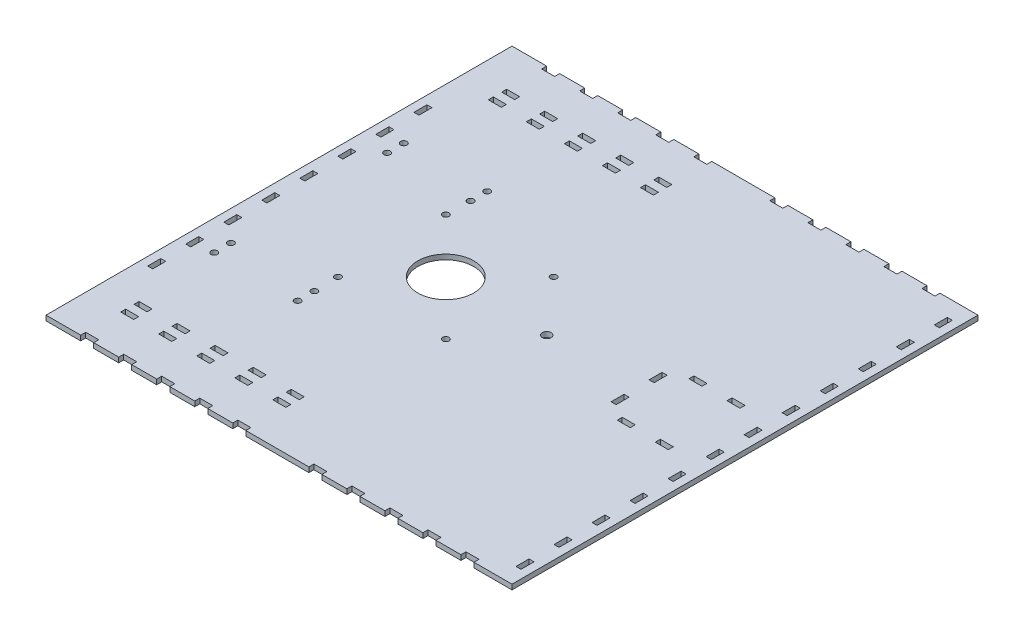
SolidWorks part; units mm, degrees
material "ENPH 253 Hardboard"
ref_plane "Front Plane" through (0, 0, 0) normal (0, 0, 1) x (1, 0, 0)
ref_plane "Top Plane" through (0, 0, 0) normal (0, 1, 0) x (1, 0, 0)
ref_plane "Right Plane" through (0, 0, 0) normal (1, 0, 0) x (0, 0, -1)
sketch "Sketch1" plane through (0, 0, 0) normal (0, 1, 0) x (1, 0, 0)
  line L0 (0, -139.7) -> (0, 139.7) construction
  line L1 (-139.7, 139.7) -> (139.7, 139.7)
  line L2 (-139.7, 139.7) -> (-139.7, -139.7)
  line L3 (-139.7, -139.7) -> (139.7, -139.7)
  line L4 (139.7, 139.7) -> (139.7, -139.7)
  line L5 (-139.7, 139.7) -> (139.7, -139.7) construction
  line L6 (-139.7, -139.7) -> (139.7, 139.7) construction
  line L12 (-139.7, 0) -> (139.7, 0) construction
  point P0 (0, 0)
  dimension "D1" = 279.4
  dimension "D2" = 279.4
extrude "Boss-Extrude1" add sketch "Sketch1" along normal blind 3
sketch "Sketch3" plane through (0, 0, 0) normal (0, -1, 0) x (-1, 0, 0)
  line L0 (-139.7, -139.7) -> (-139.7, 139.7) construction
  line L1 (-134.7, 129.3) -> (-131.7, 129.3)
  line L2 (-134.7, 129.3) -> (-134.7, 121.5)
  line L3 (-134.7, 121.5) -> (-131.7, 121.5)
  line L4 (-131.7, 129.3) -> (-131.7, 121.5)
  line L5 (-139.7, 139.7) -> (139.7, 139.7) construction
  dimension "D1" = 5
  dimension "D2" = 10.4
  dimension "D3" = 7.8
  dimension "D4" = 3
extrude "Cut-Extrude2" cut sketch "Sketch3" against normal through all
pattern_linear "LPattern1" count 12 spacing 22.8 along (0, 0, 1) of "Cut-Extrude2"
sketch "Sketch5" plane through (0, 0, 0) normal (0, -1, 0) x (1, 0, 0)
  line L0 (139.7, -139.7) -> (-139.7, -139.7) construction
  line L1 (109.1, -139.7) -> (116.9, -139.7)
  line L2 (109.1, -139.7) -> (109.1, -136.7)
  line L3 (109.1, -136.7) -> (116.9, -136.7)
  line L4 (116.9, -139.7) -> (116.9, -136.7)
  line L5 (139.7, 139.7) -> (139.7, -139.7) construction
  dimension "D1" = 22.8
  dimension "D2" = 7.8
  dimension "D3" = 3
extrude "Cut-Extrude3" cut sketch "Sketch5" against normal through all
pattern_linear "LPattern2" count 11 spacing 22.8 along (-1, 0, 0) skipping (5, 0) of "Cut-Extrude3"
mirror "Mirror2" about plane through (0, 0, 0) normal (0, 0, 1) of "LPattern2"
sketch "Sketch6" plane through (0, 0, 0) normal (0, -1, 0) x (1, 0, 0)
  line L0 (63.5, -139.7) -> (48.5, -139.7) construction
  line L1 (-134.7, -83.7) -> (-131.7, -83.7)
  line L2 (-134.7, -83.7) -> (-134.7, -75.9)
  line L3 (-134.7, -75.9) -> (-131.7, -75.9)
  line L4 (-131.7, -83.7) -> (-131.7, -75.9)
  line L5 (-139.7, -139.7) -> (-139.7, 139.7) construction
  dimension "D1" = 56
  dimension "D2" = 5
  dimension "D3" = 3
  dimension "D4" = 7.8
extrude "Cut-Extrude4" cut sketch "Sketch6" against normal through all
pattern_linear "LPattern3" count 8 spacing 22.8 along (0, 0, 1) of "Cut-Extrude4"
sketch "Sketch7" plane through (0, 0, 0) normal (0, -1, 0) x (-1, 0, 0)
  line L1 (139.7, 139.7) -> (139.7, -139.7) construction
  line L3 (-63.5, 139.7) -> (-48.5, 139.7) construction
  circle A0 centre (39.7, 0) radius 16.75
  dimension "D1" = 33.5
  dimension "D2" = 100
  dimension "D3" = 139.7
extrude "Cut-Extrude5" cut sketch "Sketch7" against normal through all
hole_wizard "#6 Clearance Hole1" positions "Sketch8" profile "Sketch9" hole size "#6" standard "ANSI Inch" end condition through all
sketch "Sketch8" plane through (0, 3, 0) normal (0, 1, 0) x (1, 0, 0)
  line L0 (-72.025, -32.325) -> (-72.025, 32.325) construction
  line L1 (-72.025, 32.325) -> (-7.375, 32.325) construction
  line L2 (-7.375, 32.325) -> (-7.375, -32.325) construction
  line L3 (-7.375, -32.325) -> (-72.025, -32.325) construction
  point P0 (-72.025, -32.325)
  point P2 (-72.025, 32.325)
  point P4 (-7.375, 32.325)
  point P6 (-7.375, -32.325)
  dimension "D1" = 64.65
  dimension "D2" = 64.65
  dimension "D3" = 90
  dimension "D4" = 64.65
  dimension "D5" = 32.325
  dimension "D6" = 32.325
sketch "Sketch9" plane through (-72.025, 3, 32.325) normal (1, 0, 0) x (0, 0, 1)
  line L0 (0, 0) -> (0, 3)
  line L1 (0, 3) -> (1.8986, 3)
  line L2 (1.8986, 3) -> (1.8986, 0)
  line L5 (1.8986, 0) -> (0, 0)
  line L11 (0, -6.35) -> (0, 107.95) construction
  dimension "Thru Hole Dia." = 3.7973
  dimension "Thru Hole Depth" = 3
hole_wizard "#6 Clearance Hole2" positions "Sketch10" profile "Sketch11" hole size "#6" standard "ANSI Inch" end condition through all
sketch "Sketch10" plane through (0, 3, 0) normal (0, 1, 0) x (1, 0, 0)
  line L0 (-139.7, 139.7) -> (-139.7, -139.7) construction
  line L1 (-118.9, 139.7) -> (-139.7, 139.7) construction
  line L2 (-139.7, -139.7) -> (-118.9, -139.7) construction
  line L3 (-73.3, 139.7) -> (-88.3, 139.7) construction
  line L4 (-88.3, -139.7) -> (-73.3, -139.7) construction
  line L5 (-139.7, 139.7) -> (-139.7, -139.7) construction
  point P0 (-121.7, 56.83)
  point P2 (-71.7, 56.83)
  point P4 (-121.7, -56.83)
  point P6 (-71.7, -56.83)
  point P22 (-71.7, -46.83)
  point P24 (-121.7, -46.83)
  point P26 (-71.7, 46.83)
  point P28 (-121.7, 46.83)
  dimension "D1" = 18
  dimension "D2" = 50
  dimension "D3" = 18
  dimension "D4" = 50
  dimension "D5" = 82.87
  dimension "D6" = 82.87
  dimension "D7" = 82.87
  dimension "D8" = 82.87
  dimension "D9" = 10
  dimension "D10" = 10
  dimension "D11" = 50
  dimension "D12" = 10
  dimension "D13" = 10
  dimension "D14" = 50
  dimension "D15" = 18
  dimension "D16" = 18
sketch "Sketch11" plane through (-121.7, 3, -56.83) normal (1, 0, 0) x (0, 0, 1)
  line L0 (0, 0) -> (0, 3)
  line L1 (0, 3) -> (1.8986, 3)
  line L2 (1.8986, 3) -> (1.8986, 0)
  line L5 (1.8986, 0) -> (0, 0)
  line L11 (0, -6.35) -> (0, 107.95) construction
  dimension "Thru Hole Dia." = 3.7973
  dimension "Thru Hole Depth" = 3
sketch "Sketch14" plane through (0, 0, 0) normal (0, -1, 0) x (-1, 0, 0)
  line L0 (139.7, 139.7) -> (139.7, -139.7) construction
  line L1 (-17.9, 139.7) -> (19.9, 139.7) construction
  circle A0 centre (-20.8, 0) radius 2.65
  dimension "D1" = 5.3
  dimension "D2" = 160.5
  dimension "D3" = 139.7
extrude "Cut-Extrude6" cut sketch "Sketch14" against normal through all
sketch "Sketch15" plane through (0, 0, 0) normal (0, -1, 0) x (-1, 0, 0)
  line L0 (139.7, 139.7) -> (139.7, -139.7) construction
  line L1 (111.1, -112.7) -> (118.9, -112.7)
  line L2 (111.1, -112.7) -> (111.1, -115.7)
  line L3 (111.1, -115.7) -> (118.9, -115.7)
  line L4 (118.9, -112.7) -> (118.9, -115.7)
  line L5 (139.7, -139.7) -> (118.9, -139.7) construction
  dimension "D1" = 20.8
  dimension "D2" = 7.8
  dimension "D3" = 3
  dimension "D4" = 24
extrude "Cut-Extrude7" cut sketch "Sketch15" against normal through all
pattern_linear "LPattern4" count 5 spacing 22.8 along (1, 0, 0) of "Cut-Extrude7"
mirror "Mirror3" about plane through (0, 0, 0) normal (0, 0, 1) of "LPattern4"
sketch "Sketch16" plane through (0, 0, 0) normal (0, -1, 0) x (1, 0, 0)
  line L0 (-139.7, -139.7) -> (-139.7, 139.7) construction
  line L1 (-118.9, 107.7) -> (-111.1, 107.7)
  line L2 (-118.9, 107.7) -> (-118.9, 104.7)
  line L3 (-118.9, 104.7) -> (-111.1, 104.7)
  line L4 (-111.1, 107.7) -> (-111.1, 104.7)
  line L5 (-118.9, 112.7) -> (-111.1, 112.7) construction
  dimension "D1" = 20.8
  dimension "D2" = 7.8
  dimension "D3" = 5
  dimension "D4" = 3
extrude "Cut-Extrude8" cut sketch "Sketch16" against normal through all
pattern_linear "LPattern5" count 5 spacing 22.8 along (1, 0, 0) of "Cut-Extrude8"
mirror "Mirror4" about plane through (0, 0, 0) normal (0, 0, 1) of "LPattern5"
sketch "Sketch17" plane through (0, 0, 0) normal (0, -1, 0) x (1, 0, 0)
  line L1 (116.7, 23) -> (108.9, 23)
  line L2 (116.7, 23) -> (116.7, 20)
  line L3 (116.7, 20) -> (108.9, 20)
  line L4 (108.9, 23) -> (108.9, 20)
  line L5 (94.1, 139.7) -> (109.1, 139.7) construction
  line L6 (139.7, 139.7) -> (139.7, -139.7) construction
  point P8 (116.7, 21.5)
  dimension "D1" = 116.7
  dimension "D2" = 23
  dimension "D3" = 7.8
  dimension "D4" = 3
extrude "Cut-Extrude9" cut sketch "Sketch17" against normal through all
pattern_linear "LPattern6" count 2 spacing 22.8 along (-1, 0, 0) of "Cut-Extrude9"
sketch "Sketch18" plane through (0, 0, 0) normal (0, -1, 0) x (-1, 0, 0)
  line L0 (-139.7, -139.7) -> (-139.7, 139.7) construction
  line L1 (-77.7, -15.3) -> (-74.7, -15.3)
  line L2 (-77.7, -15.3) -> (-77.7, -7.5)
  line L3 (-77.7, -7.5) -> (-74.7, -7.5)
  line L4 (-74.7, -15.3) -> (-74.7, -7.5)
  line L5 (-71.3, -139.7) -> (-86.3, -139.7) construction
  dimension "D1" = 7.8
  dimension "D2" = 3
  dimension "D3" = 62
  dimension "D4" = 124.4
extrude "Cut-Extrude10" cut sketch "Sketch18" against normal through all
mirror "Mirror5" about plane through (0, 0, 0) normal (0, 0, 1) of "Cut-Extrude10", "LPattern6", "Cut-Extrude9"
